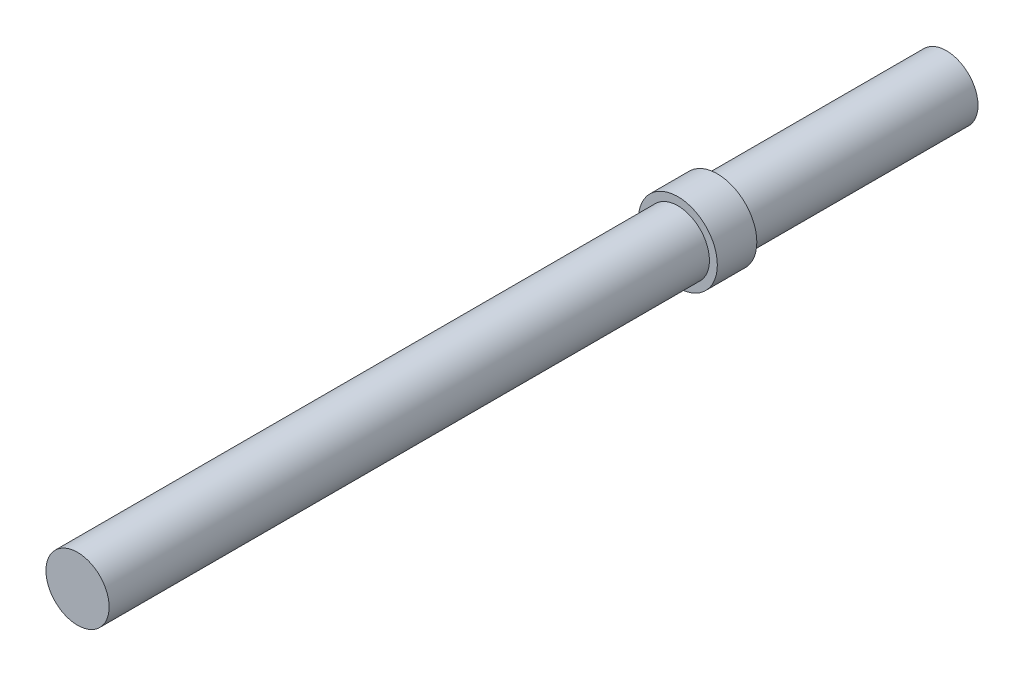
SolidWorks part; units mm, degrees
ref_plane "Alzado" through (0, 0, 0) normal (0, 0, 1) x (1, 0, 0)
ref_plane "Planta" through (0, 0, 0) normal (0, 1, 0) x (1, 0, 0)
ref_plane "Vista lateral" through (0, 0, 0) normal (1, 0, 0) x (0, 0, -1)
sketch "Croquis1" plane through (0, 0, 0) normal (0, 0, 1) x (1, 0, 0)
  circle A0 centre (0, 0) radius 4
  dimension "D1" = 8
extrude "Saliente-Extruir1" add sketch "Croquis1" along normal mid plane 110
ref_plane "Plano2" through (3, 0, 0) normal (1, 0, 0) x (0, 0, -1)
ref_plane "Plano3" through (0, 0, -26) normal (0, 0, 1) x (1, 0, 0)
sketch "Croquis2" plane through (0, 0, -26) normal (0, 0, 1) x (1, 0, 0)
  circle A0 centre (0, 0) radius 5
  dimension "D1" = 10
extrude "Saliente-Extruir2" add sketch "Croquis2" along normal blind 5
